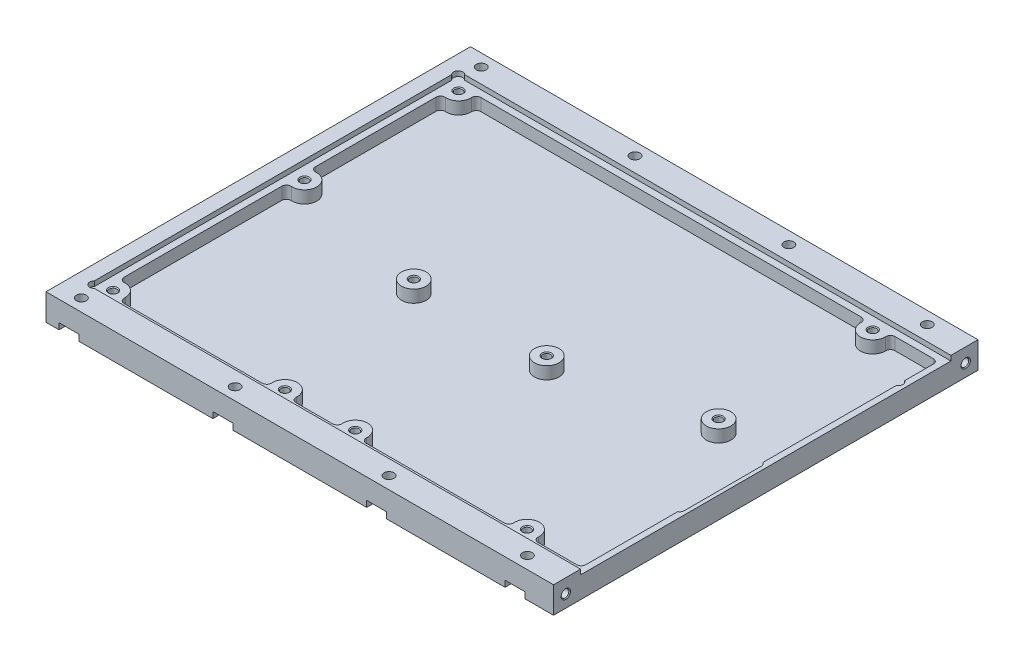
SolidWorks part; units mm, degrees
ref_plane "Front Plane" through (0, 0, 0) normal (0, 0, 1) x (1, 0, 0)
ref_plane "Top Plane" through (0, 0, 0) normal (0, 1, 0) x (1, 0, 0)
ref_plane "Right Plane" through (0, 0, 0) normal (1, 0, 0) x (0, 0, -1)
sketch "Sketch1" plane through (0, 0, 0) normal (0, 1, 0) x (1, 0, 0)
  line L1 (-85, 69) -> (80, 69)
  line L2 (-85, 69) -> (-85, -69)
  line L3 (-85, -69) -> (80, -69)
  line L4 (80, 69) -> (80, -69)
  dimension "D1" = 165
  dimension "D2" = 138
  dimension "D3" = 80
  dimension "D4" = 69
extrude "Boss-Extrude1" add sketch "Sketch1" along normal blind 7
sketch "Sketch4" plane through (0, 7, 0) normal (0, 1, 0) x (1, 0, 0)
  circle A0 centre (-76.1, -56.1) radius 1.25
  circle A1 centre (-20.22, -56.1) radius 1.25
  circle A2 centre (2.64, -56.1) radius 1.25
  circle A3 centre (58.49, -56.1) radius 1.25
  circle A4 centre (-76.1, 6.13) radius 1.25
  circle A5 centre (-30.38, -4.03) radius 1.25
  circle A6 centre (58.52, 6.16) radius 1.25
  circle A7 centre (12.8, -4) radius 1.25
  dimension "D1" = 2.5
  dimension "D2" = 2.5
  dimension "D3" = 2.5
  dimension "D4" = 2.5
  dimension "D5" = 2.5
  dimension "D6" = 2.5
  dimension "D7" = 2.5
  dimension "D8" = 2.5
  dimension "D9" = 22.86
  dimension "D10" = 55.88
  dimension "D11" = 55.85
  dimension "D12" = 45.72
  dimension "D13" = 10.16
  dimension "D14" = 62.23
  dimension "D15" = 62.26
  dimension "D16" = 10.16
  dimension "D17" = 45.72
  dimension "D18" = 43.18
  dimension "D19" = 12.8
  dimension "D20" = 4
extrude "Cut-Extrude2" cut sketch "Sketch4" against normal blind 5
cosmetic thread "Hole Thread9" parameters "D1"=4.45, "D2"=3
cosmetic thread "Hole Thread10" parameters "D1"=4.45, "D2"=3
cosmetic thread "Hole Thread11" parameters "D1"=4.45, "D2"=3
cosmetic thread "Hole Thread12" parameters "D1"=4.45, "D2"=3
cosmetic thread "Hole Thread13" parameters "D1"=4.45, "D2"=3
cosmetic thread "Hole Thread14" parameters "D1"=4.45, "D2"=3
cosmetic thread "Hole Thread15" parameters "D1"=4.45, "D2"=3
cosmetic thread "Hole Thread16" parameters "D1"=4.45, "D2"=3
cosmetic thread "Hole Thread17" parameters "D1"=4.45, "D2"=3
cosmetic thread "Hole Thread18" parameters "D1"=4.45, "D2"=3
cosmetic thread "Hole Thread19" parameters "D1"=4.45, "D2"=3
cosmetic thread "Hole Thread20" parameters "D1"=4.45, "D2"=3
cosmetic thread "Hole Thread21" parameters "D1"=4.45, "D2"=3
cosmetic thread "Hole Thread22" parameters "D1"=4.45, "D2"=3
cosmetic thread "Hole Thread23" parameters "D1"=4.45, "D2"=3
cosmetic thread "Hole Thread24" parameters "D1"=4.45, "D2"=3
cosmetic thread "Hole Thread25" parameters "D1"=4.45, "D2"=3
cosmetic thread "Hole Thread26" parameters "D1"=4.45, "D2"=3
cosmetic thread "Hole Thread27" parameters "D1"=4.45, "D2"=3
cosmetic thread "Hole Thread28" parameters "D1"=4.45, "D2"=3
cosmetic thread "Hole Thread29" parameters "D1"=4.45, "D2"=3
cosmetic thread "Hole Thread30" parameters "D1"=4.45, "D2"=3
cosmetic thread "Hole Thread31" parameters "D1"=4.45, "D2"=3
cosmetic thread "Hole Thread32" parameters "D1"=4.45, "D2"=3
sketch "Sketch5" plane through (0, 7, 0) normal (0, -1, 0) x (-1, 0, 0)
  line L0 (70.6, -58) -> (25.7054, -58)
  line L1 (-78, -56.5) -> (-78, -26.6266)
  line L3 (78, -50.6) -> (78, 0.6446)
  line L5 (-78.8, -25.3) -> (-78.8, -0.3)
  line L7 (14.7346, -58) -> (2.8454, -58)
  line L8 (-8.1254, -58) -> (-53.0046, -58)
  line L9 (-63.9754, -58) -> (-76.5, -58)
  line L11 (72.1, -56.1) -> (72.1, -56.5)
  line L12 (76.1, -52.1) -> (76.5, -52.1)
  line L13 (70.6061, 58) -> (-53.0248, 58)
  line L14 (-78, 1.0266) -> (-78, 44.4734)
  line L15 (78, 11.6154) -> (78, 50.7546)
  line L16 (-64.0152, 58) -> (-76.5, 58)
  line L17 (-78, 1.0266) -> (-78, -26.6266) construction
  line L18 (-78, -12.8) -> (-78.8, -12.8) construction
  line L19 (-78, 47.1266) -> (-78, 56.5)
  arc A0 (76.1, -52.1) -> (72.1, -56.1) centre (76.1, -56.1) ccw
  arc A1 (24.2094, -56.3909) -> (16.2306, -56.3909) centre (20.22, -56.1) ccw
  arc A2 (1.3494, -56.3909) -> (-6.6294, -56.3909) centre (-2.64, -56.1) ccw
  arc A3 (-54.5006, -56.3909) -> (-62.4794, -56.3909) centre (-58.49, -56.1) ccw
  circle A6 centre (30.38, -4.03) radius 4
  circle A7 centre (-12.8, -4) radius 4
  arc A8 (70.6, -58) -> (72.1, -56.5) centre (70.6, -56.5) ccw
  arc A9 (78, -50.6) -> (76.5, -52.1) centre (76.5, -50.6) cw
  arc A15 (-78, -56.5) -> (-76.5, -58) centre (-76.5, -56.5) ccw
  arc A16 (-63.9754, -58) -> (-62.4794, -56.3909) centre (-63.9754, -56.5) ccw
  arc A17 (-53.0046, -58) -> (-54.5006, -56.3909) centre (-53.0046, -56.5) cw
  arc A18 (-8.1254, -58) -> (-6.6294, -56.3909) centre (-8.1254, -56.5) ccw
  arc A19 (2.8454, -58) -> (1.3494, -56.3909) centre (2.8454, -56.5) cw
  arc A20 (14.7346, -58) -> (16.2306, -56.3909) centre (14.7346, -56.5) ccw
  arc A21 (24.2094, -56.3909) -> (25.7054, -58) centre (25.7054, -56.5) ccw
  arc A22 (76.3909, 10.1194) -> (76.3909, 2.1406) centre (76.1, 6.13) ccw
  circle A23 centre (-58.52, 6.16) radius 4
  arc A24 (78, 11.6154) -> (76.3909, 10.1194) centre (76.5, 11.6154) cw
  arc A25 (76.3909, 2.1406) -> (78, 0.6446) centre (76.5, 0.6446) cw
  arc A26 (-78, 56.5) -> (-76.5, 58) centre (-76.5, 56.5) cw
  arc A28 (72.1045, 56.4291) -> (76.3909, 52.2506) centre (76.1, 56.24) ccw
  arc A29 (72.1045, 56.4291) -> (70.6061, 58) centre (70.6061, 56.5) ccw
  arc A30 (76.3909, 52.2506) -> (78, 50.7546) centre (76.5, 50.7546) cw
  arc A31 (-62.5165, 56.4373) -> (-54.5235, 56.4373) centre (-58.52, 56.27) ccw
  arc A32 (-62.5165, 56.4373) -> (-64.0152, 58) centre (-64.0152, 56.5) ccw
  arc A33 (-54.5235, 56.4373) -> (-53.0248, 58) centre (-53.0248, 56.5) cw
  arc A34 (-78.8, -25.3) -> (-78, -26.6266) centre (-77.3, -25.3) ccw
  arc A35 (-78, 1.0266) -> (-78.8, -0.3) centre (-77.3, -0.3) ccw
  arc A36 (-78, 47.1266) -> (-78, 44.4734) centre (-77.3, 45.8) ccw
  point P47 (78, 9.6499)
  point P59 (-62.0099, -58)
  point P64 (-6.1599, -58)
  point P69 (16.7001, -58)
  point P82 (-62.1265, 58)
  dimension "D1" = 8
  dimension "D2" = 8
  dimension "D3" = 58
  dimension "D4" = 8
  dimension "D5" = 8
  dimension "D6" = 8
  dimension "D7" = 8
  dimension "D8" = 8
  dimension "D13" = 1.5
  dimension "D14" = 1.5
  dimension "D15" = 1.5
  dimension "D12" = 8
  dimension "D16" = 1.5
  dimension "D17" = 1.5
  dimension "D18" = 8
  dimension "D20" = 1.5
  dimension "D21" = 8
  dimension "D23" = 1.5
  dimension "D27" = 25
  dimension "D28" = 12.2
  dimension "D26" = 1.5
  dimension "D29" = 3
  dimension "D9" = 58
  dimension "D10" = 78
  dimension "D11" = 78
  dimension "D19" = 50.11
  dimension "D22" = 50.11
  dimension "D24" = 0.8
  dimension "D25" = 45.2
extrude "Cut-Extrude3" cut sketch "Sketch5" along normal blind 4
sketch "Sketch6" plane through (0, 7, 0) normal (0, 1, 0) x (1, 0, 0)
  line L0 (-79.1393, 59.1393) -> (-80.2, 60.2) construction
  line L5 (-78.0787, 60.2) -> (80, 60.2)
  line L6 (-80.2, 58.0787) -> (-80.2, -58.0787)
  line L7 (-78.0787, -60.2) -> (80, -60.2)
  line L9 (80, -69) -> (80, 69) construction
  line L10 (-80.2, -60.2) -> (-79.1393, -59.1393) construction
  line L14 (80, 60.2) -> (80, 69)
  line L15 (80, 69) -> (-85, 69)
  line L16 (-85, 69) -> (-85, -69)
  line L17 (-85, -69) -> (80, -69)
  line L18 (80, -60.2) -> (80, -69)
  arc A0 (-78.0787, 60.2) -> (-80.2, 58.0787) centre (-79.1393, 59.1393) ccw
  arc A2 (-80.2, -58.0787) -> (-78.0787, -60.2) centre (-79.1393, -59.1393) ccw
  dimension "D5" = 3
  dimension "D13" = 3
  dimension "D2" = 120.4
  dimension "D3" = 80.2
  dimension "D4" = 60.2
  dimension "D6" = 45
  dimension "D7" = 1.0607
  dimension "D8" = 1.0607
  dimension "D14" = 45
  dimension "D15" = 1.0607
  dimension "D16" = 1.0607
extrude "Boss-Extrude2" add sketch "Sketch6" along normal blind 1.6
sketch "Sketch7" plane through (0, 8.6, 0) normal (0, 1, 0) x (1, 0, 0)
  line L5 (80, -60.2) -> (-78.0787, -60.2) construction
  line L6 (-85, -69) -> (80, -69) construction
  circle A0 centre (-77.5, -65) radius 1.6
  circle A1 centre (-27.5, -65) radius 1.6
  circle A2 centre (22.5, -65) radius 1.6
  circle A3 centre (67.5, -65) radius 1.6
  circle A4 centre (-77.5, 65) radius 1.6
  circle A5 centre (-27.5, 65) radius 1.6
  circle A6 centre (22.5, 65) radius 1.6
  circle A7 centre (67.5, 65) radius 1.6
  dimension "D5" = 3.2
  dimension "D6" = 3.2
  dimension "D7" = 3.2
  dimension "D8" = 3.2
  dimension "D11" = 3.2
  dimension "D12" = 3.2
  dimension "D13" = 3.2
  dimension "D14" = 3.2
  dimension "D1" = 50
  dimension "D2" = 45
  dimension "D3" = 50
  dimension "D4" = 27.5
  dimension "D9" = 65
  dimension "D10" = 65
  dimension "D15" = 4.8
  dimension "D16" = 4
extrude "Cut-Extrude4" cut sketch "Sketch7" against normal up to next
sketch "Sketch8" plane through (0, 0, 0) normal (0, -1, 0) x (-1, 0, 0)
  line L0 (-70.75, -65) -> (-70.75, -69)
  line L1 (85, -69) -> (-80, -69) construction
  line L2 (-64.25, -65) -> (-64.25, -69)
  line L3 (-64.25, -69) -> (-70.75, -69)
  line L4 (-25.75, -65) -> (-25.75, -69)
  line L5 (-19.25, -65) -> (-19.25, -69)
  line L6 (-19.25, -69) -> (-25.75, -69)
  line L7 (24.25, -65) -> (24.25, -69)
  line L8 (30.75, -65) -> (30.75, -69)
  line L9 (30.75, -69) -> (24.25, -69)
  line L10 (74.25, -65) -> (74.25, -69)
  line L11 (80.75, -65) -> (80.75, -69)
  line L12 (80.75, -69) -> (74.25, -69)
  line L13 (80.75, 65) -> (80.75, 69)
  line L16 (80.75, 69) -> (74.25, 69)
  line L17 (-80, 69) -> (85, 69) construction
  line L18 (74.25, 69) -> (74.25, 65)
  line L19 (30.75, 65) -> (30.75, 69)
  line L20 (30.75, 69) -> (24.25, 69)
  line L21 (24.25, 69) -> (24.25, 65)
  line L22 (-19.25, 65) -> (-19.25, 69)
  line L23 (-19.25, 69) -> (-25.75, 69)
  line L24 (-25.75, 69) -> (-25.75, 65)
  line L25 (-64.25, 65) -> (-64.25, 69)
  line L26 (-64.25, 69) -> (-70.75, 69)
  line L27 (-70.75, 69) -> (-70.75, 65)
  arc A0 (-19.25, -65) -> (-25.75, -65) centre (-22.5, -65) ccw
  arc A1 (30.75, -65) -> (24.25, -65) centre (27.5, -65) ccw
  arc A2 (-64.25, -65) -> (-70.75, -65) centre (-67.5, -65) ccw
  arc A3 (80.75, -65) -> (74.25, -65) centre (77.5, -65) ccw
  arc A4 (74.25, 65) -> (80.75, 65) centre (77.5, 65) ccw
  arc A5 (24.25, 65) -> (30.75, 65) centre (27.5, 65) ccw
  arc A6 (-25.75, 65) -> (-19.25, 65) centre (-22.5, 65) ccw
  arc A7 (-70.75, 65) -> (-64.25, 65) centre (-67.5, 65) ccw
  dimension "D1" = 6.5
  dimension "D2" = 6.5
  dimension "D3" = 6.5
  dimension "D4" = 6.5
  dimension "D5" = 6.5
  dimension "D6" = 6.5
  dimension "D7" = 6.5
  dimension "D8" = 6.5
extrude "Cut-Extrude5" cut sketch "Sketch8" against normal blind 2
hole_wizard "M3 Tapped Hole1" positions "Sketch9" profile "Sketch10" tap size "M3" standard "ISO"
sketch "Sketch9" plane through (0, 0, 0) normal (0, -1, 0) x (-1, 0, 0)
  point P0 (70, -64.6)
  point P2 (2.5, -64.6)
  point P4 (-60, -64.6)
  point P6 (2.5, 64.6)
  point P8 (70, 64.6)
  point P10 (-60, 64.6)
  dimension "D1" = 64.6
  dimension "D2" = 64.6
  dimension "D3" = 70
  dimension "D4" = 60
  dimension "D5" = 2.5
sketch "Sketch10" plane through (-70, 0, 64.6) normal (1, 0, 0) x (0, 0, -1)
  line L0 (0, 0) -> (0, 8.2511)
  line L1 (0, 8.2511) -> (1.25, 7.5)
  line L2 (1.25, 7.5) -> (1.25, 0.275)
  line L3 (1.25, 0.275) -> (1.525, 0)
  line L5 (1.525, 0) -> (0, 0)
  line L6 (-1.25, 0.275) -> (-1.525, 0) construction
  line L10 (0, 8.2511) -> (-1.25, 7.5) construction
  line L11 (0, -6.35) -> (0, 107.95) construction
  dimension "Tap Drill Dia." = 2.5
  dimension "Tap Drill Depth" = 7.5
  dimension "Near C'Sink Dia." = 3.05
  dimension "Near C'Sink Angle" = 90
  dimension "Drill Angle" = 118
cosmetic thread "Hole Thread1" parameters "D1"=6, "D2"=3
cosmetic thread "Hole Thread2" parameters "D1"=6, "D2"=3
cosmetic thread "Hole Thread3" parameters "D1"=6, "D2"=3
cosmetic thread "Hole Thread4" parameters "D1"=6, "D2"=3
cosmetic thread "Hole Thread5" parameters "D1"=6, "D2"=3
cosmetic thread "Hole Thread6" parameters "D1"=6, "D2"=3
hole_wizard "M3 Tapped Hole2" positions "Sketch12" profile "Sketch11" tap size "M3" standard "ISO"
sketch "Sketch12" plane through (80, 0, 0) normal (1, 0, 0) x (0, 0, -1)
  line L0 (-69, 0) -> (69, 0) construction
  point P0 (-65, 4)
  point P1 (65, 4)
  dimension "D1" = 65
  dimension "D2" = 65
  dimension "D3" = 4
sketch "Sketch11" plane through (80, 4, 65) normal (0, 1, 0) x (0, 0, -1)
  line L0 (0, 0) -> (0, 8.2511)
  line L1 (0, 8.2511) -> (1.25, 7.5)
  line L2 (1.25, 7.5) -> (1.25, 0.275)
  line L3 (1.25, 0.275) -> (1.525, 0)
  line L5 (1.525, 0) -> (0, 0)
  line L6 (-1.25, 0.275) -> (-1.525, 0) construction
  line L10 (0, 8.2511) -> (-1.25, 7.5) construction
  line L11 (0, -6.35) -> (0, 107.95) construction
  dimension "Tap Drill Dia." = 2.5
  dimension "Tap Drill Depth" = 7.5
  dimension "Near C'Sink Dia." = 3.05
  dimension "Near C'Sink Angle" = 90
  dimension "Drill Angle" = 118
cosmetic thread "Hole Thread7" parameters "D1"=6, "D2"=3
cosmetic thread "Hole Thread8" parameters "D1"=6, "D2"=3
hole_wizard "M3 Tapped Hole3" positions "Sketch13" profile "Sketch14" tap size "M3" standard "ISO"
sketch "Sketch13" plane through (0, 7, 0) normal (0, 1, 0) x (1, 0, 0)
  point P0 (-76.1, 6.13)
  point P3 (-30.38, -4.03)
  point P6 (12.8, -4)
  point P9 (58.52, 6.16)
  point P12 (-76.1, -56.1)
  point P15 (-20.22, -56.1)
  point P18 (2.64, -56.1)
  point P21 (58.49, -56.1)
  point P24 (-76.1, 56.24)
  point P27 (58.52, 56.27)
sketch "Sketch14" plane through (-76.1, 7, -6.13) normal (1, 0, 0) x (0, 0, 1)
  line L0 (0, 0) -> (0, 5.7511)
  line L1 (0, 5.7511) -> (1.25, 5)
  line L2 (1.25, 5) -> (1.25, 0.275)
  line L3 (1.25, 0.275) -> (1.525, 0)
  line L5 (1.525, 0) -> (0, 0)
  line L6 (-1.25, 0.275) -> (-1.525, 0) construction
  line L10 (0, 5.7511) -> (-1.25, 5) construction
  line L11 (0, -6.35) -> (0, 107.95) construction
  dimension "Tap Drill Dia." = 2.5
  dimension "Tap Drill Depth" = 5
  dimension "Near C'Sink Dia." = 3.05
  dimension "Near C'Sink Angle" = 90
  dimension "Drill Angle" = 118
cosmetic thread "Hole Thread33" parameters "D1"=0, "D2"=3.5
cosmetic thread "Hole Thread34" parameters "D1"=0, "D2"=3.5
